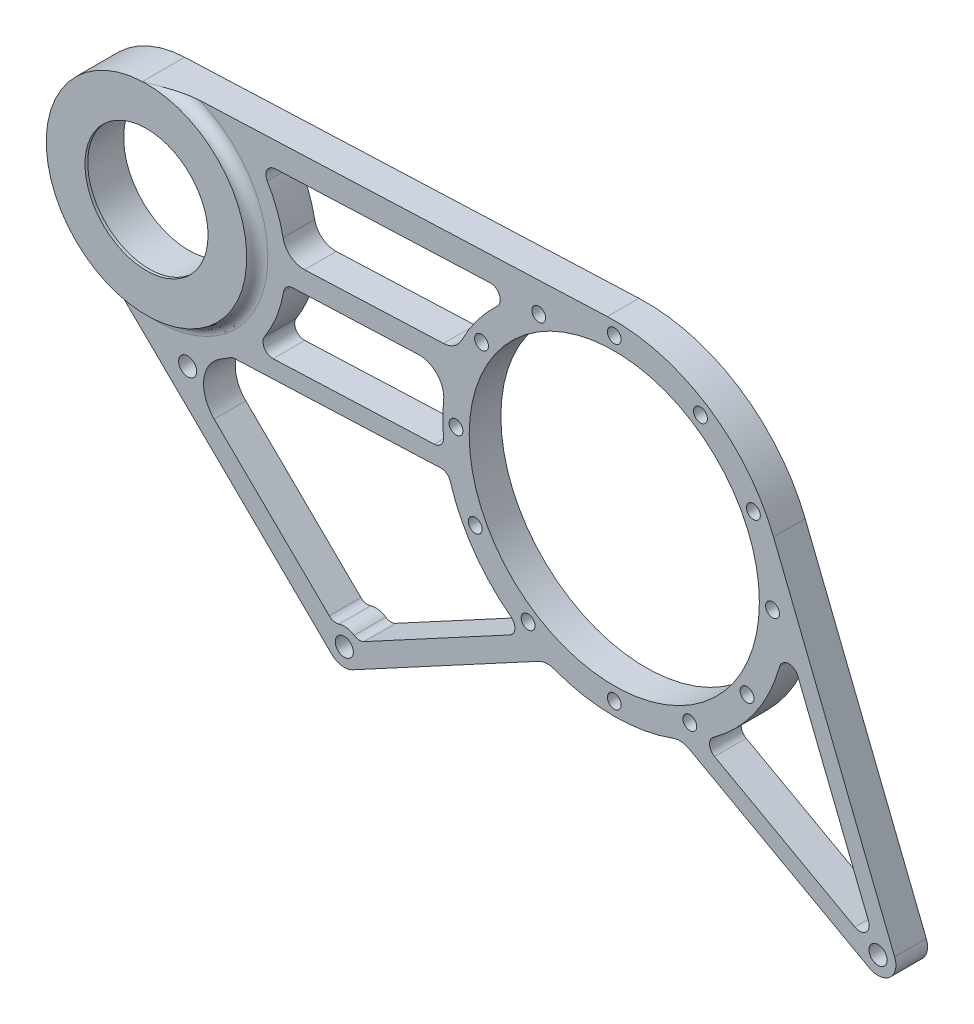
SolidWorks part; units mm, degrees
material "6061-T6 (SS)"
ref_plane "Front Plane" through (0, 0, 0) normal (0, 0, 1) x (1, 0, 0)
ref_plane "Top Plane" through (0, 0, 0) normal (0, 1, 0) x (1, 0, 0)
ref_plane "Right Plane" through (0, 0, 0) normal (1, 0, 0) x (0, 0, -1)
sketch "Sketch1" plane through (0, 0, 0) normal (0, 0, 1) x (1, 0, 0)
  line L0 (-114.3, 95.25) -> (-114.3, 107.95) construction
  line L1 (-280.8642, 163.1704) -> (-116.8043, 169.8118)
  line L2 (-304.7421, 101.1501) -> (-216.3071, 14.4521)
  line L3 (-13.0706, 21.4387) -> (-56.8054, 130.918)
  line L4 (-208.742, 13.3833) -> (-141.7118, 49.5504)
  line L5 (-22.1639, 13.4141) -> (-87.2342, 49.3665)
  circle A0 centre (-279.4, 127) radius 23.5
  circle A1 centre (-114.3, 95.25) radius 36 construction
  circle A2 centre (0, 0) radius 12.7 construction
  circle A3 centre (-228.6, 0) radius 12.7 construction
  circle A4 centre (-114.3, 107.95) radius 52.3875
  circle A5 centre (-19.05, 19.05) radius 3.2639
  circle A6 centre (-211.7995, 19.05) radius 3.2639
  circle A7 centre (-279.4, 127) radius 36.2
  arc A8 (-135.9521, 49.947) -> (-93.0137, 49.8118) centre (-114.3, 107.95) ccw
  arc A9 (-216.3071, 14.4521) -> (-208.742, 13.3833) centre (-211.7995, 19.05) ccw
  arc A10 (-22.1639, 13.4141) -> (-13.0706, 21.4387) centre (-19.05, 19.05) ccw
  arc A11 (-56.8054, 130.918) -> (-116.8043, 169.8118) centre (-114.3, 107.95) ccw
  arc A12 (-135.9521, 49.947) -> (-141.7118, 49.5504) centre (-138.3949, 43.4031) ccw
  arc A13 (-87.2342, 49.3665) -> (-93.0137, 49.8118) centre (-90.6122, 43.2526) ccw
  dimension "D5" = 72
  dimension "D6" = 47
  dimension "D7" = 25.4
  dimension "D8" = 25.4
  dimension "D11" = 104.775
  dimension "D14" = 6.5278
  dimension "D15" = 6.5278
  dimension "D16" = 25.4
  dimension "D17" = 12.7
  dimension "D18" = 123.825
  dimension "D19" = 3.175
  dimension "D20" = 6.985
  dimension "D21" = 6.985
  dimension "D1" = 114.3
  dimension "D2" = 95.25
  dimension "D3" = 279.4
  dimension "D4" = 127
  dimension "D9" = 228.6
  dimension "D10" = 12.7
  dimension "D12" = 19.05
  dimension "D13" = 19.05
extrude "Boss-Extrude1" add sketch "Sketch1" along normal blind 11.43 contours A13 L5 A10 L3 A11 L1 A7 L2 A9 L4 A12 A8 A6 A5 A4 | A7 A0 region at (-168.693, 91.0379, 0) region at (-255.035, 152.3713, 0)
sketch "Sketch2" plane through (0, 0, 11.43) normal (0, 0, 1) x (1, 0, 0)
  circle A0 centre (-279.4, 127) radius 36.2
  circle A1 centre (-279.4, 127) radius 23.5
extrude "Boss-Extrude2" add sketch "Sketch2" along normal blind 3.81
fillet "Fillet1" radius 3.81 1 edges at (-245.6173, 113.9936, 11.43)
sketch "Sketch3" plane through (0, 0, 11.43) normal (0, 0, 1) x (1, 0, 0)
  line L0 (-114.3, 107.95) -> (-114.3, 165.1) construction
  line L1 (-114.3, 107.95) -> (-57.15, 107.95) construction
  line L2 (-114.3, 107.95) -> (-83.1739, 155.88) construction
  line L3 (-114.3, 107.95) -> (-64.0756, 135.2196) construction
  circle A0 centre (-114.3, 107.95) radius 57.15 construction
  circle A11 centre (-114.3, 165.1) radius 2.5
  circle A12 centre (-57.15, 107.95) radius 2.5
  circle A13 centre (-114.3, 50.8) radius 2.5
  circle A14 centre (-171.45, 107.95) radius 2.5
  circle A15 centre (-83.1739, 155.88) radius 2.5
  circle A16 centre (-64.0756, 135.2196) radius 2.5
  circle A17 centre (-66.37, 76.8239) radius 2.5
  circle A18 centre (-87.0304, 57.7256) radius 2.5
  circle A19 centre (-145.4261, 60.02) radius 2.5
  circle A20 centre (-164.5244, 80.6804) radius 2.5
  circle A21 centre (-162.23, 139.0761) radius 2.5
  circle A22 centre (-141.5696, 158.1744) radius 2.5
  point P14 (-114.3, 107.95)
  point P25 (-114.3, 107.95)
  point P33 (-114.3, 107.95)
  dimension "D1" = 114.3
  dimension "D2" = 5
  dimension "D6" = 5
  dimension "D4" = 33
  dimension "D5" = 61.5
  dimension "D3" = 4
  dimension "D7" = 4
extrude "5mm Holes" cut sketch "Sketch3" against normal through all
sketch "Sketch4" plane through (0, 0, 15.24) normal (0, 0, 1) x (1, 0, 0)
  circle A0 centre (-279.4, 127) radius 22.225
  circle A1 centre (-279.4, 127) radius 23.5 construction
  circle A2 centre (-279.4, 127) radius 23.5
  dimension "D1" = 44.45
extrude "Boss-Extrude3" add sketch "Sketch4" against normal blind 1
sketch "Sketch5" plane through (0, 0, 11.43) normal (0, 0, 1) x (1, 0, 0)
  line L0 (-48.0193, 91.8071) -> (-22.5033, 27.9342)
  line L1 (-13.0706, 21.4387) -> (-56.8054, 130.918) construction
  line L2 (-78.1047, 51.5771) -> (-27.4356, 23.5816)
  line L3 (-22.1639, 13.4141) -> (-87.2342, 49.3665) construction
  line L4 (-236.7455, 156.0591) -> (-159.125, 159.2013)
  line L5 (-263.8382, 163.8596) -> (-116.8043, 169.8118) construction
  line L6 (-226.1253, 129.7972) -> (-175.9845, 131.827)
  line L7 (-230.4174, 121.9972) -> (-185.1154, 123.8311)
  line L8 (-258.7869, 66.7686) -> (-217.2302, 26.028)
  line L9 (-204.6483, 24.2506) -> (-152.0143, 52.6499)
  line L10 (-292.5742, 89.2212) -> (-216.3071, 14.4521) construction
  line L11 (-208.742, 13.3833) -> (-141.7118, 49.5504) construction
  line L12 (-237.4937, 96.2899) -> (-179.3047, 98.6455)
  line L13 (-251.3498, 89.3738) -> (-177.0086, 92.3833)
  arc A0 (-175.0426, 119.9291) -> (-175.9673, 102.4457) centre (-114.3, 107.95) ccw construction
  circle A1 centre (-211.7995, 19.05) radius 6.4389 construction
  circle A2 centre (-19.05, 19.05) radius 6.4389 construction
  arc A3 (-54.6287, 91.4427) -> (-78.4387, 57.481) centre (-114.3, 107.95) cw
  arc A4 (-48.0193, 91.8071) -> (-54.6287, 91.4427) centre (-51.2626, 90.5115) ccw
  arc A5 (-27.4356, 23.5816) -> (-22.5033, 27.9342) centre (-25.7466, 26.6385) ccw
  arc A6 (-78.1047, 51.5771) -> (-78.4387, 57.481) centre (-76.4157, 54.634) cw
  arc A7 (-233.9104, 135.9413) -> (-239.6024, 150.7781) centre (-279.4, 127) ccw construction
  arc A8 (-292.5742, 89.2212) -> (-263.8382, 163.8596) centre (-279.4, 127) ccw construction
  arc A9 (-213.7352, 25.191) -> (-208.2383, 24.4145) centre (-211.7995, 19.05) cw
  arc A10 (-156.5977, 153.1613) -> (-169.499, 135.9897) centre (-114.3, 107.95) ccw
  arc A11 (-175.9093, 114.0697) -> (-175.9673, 102.4457) centre (-114.3, 107.95) ccw
  arc A12 (-173.5263, 89.9112) -> (-151.5703, 58.5123) centre (-114.3, 107.95) ccw
  arc A13 (-239.6024, 150.7781) -> (-233.9104, 135.9413) centre (-279.4, 127) cw
  arc A14 (-233.7176, 119.1025) -> (-240.5609, 101.6865) centre (-279.4, 127) cw
  arc A15 (-240.5609, 101.6865) -> (-233.7176, 119.1025) centre (-279.4, 127) ccw construction
  arc A16 (-253.1835, 88.7646) -> (-256.2406, 86.8392) centre (-279.4, 127) cw
  arc A17 (-159.125, 159.2013) -> (-156.5977, 153.1613) centre (-158.9837, 155.7117) cw
  arc A20 (-236.7455, 156.0591) -> (-239.6024, 150.7781) centre (-236.6043, 152.5695) ccw
  arc A21 (-179.3047, 98.6455) -> (-175.9673, 102.4457) centre (-179.446, 102.1352) ccw
  arc A23 (-230.4174, 121.9972) -> (-233.7176, 119.1025) centre (-230.2762, 118.5075) ccw
  arc A24 (-237.4937, 96.2899) -> (-240.5609, 101.6865) centre (-237.6349, 99.7796) cw
  arc A25 (-217.2302, 26.028) -> (-213.7352, 25.191) centre (-214.7852, 28.522) ccw
  arc A26 (-204.6483, 24.2506) -> (-208.2383, 24.4145) centre (-206.3067, 27.3242) cw
  arc A27 (-152.0143, 52.6499) -> (-151.5703, 58.5123) centre (-153.6727, 55.7236) ccw
  arc A28 (-177.0086, 92.3833) -> (-173.5263, 89.9112) centre (-176.8673, 88.8936) cw
  arc A29 (-251.3498, 89.3738) -> (-253.1835, 88.7646) centre (-251.2085, 85.8842) ccw
  arc A31 (-173.5263, 89.9112) -> (-170.4887, 133.9499) centre (-114.3, 107.95) ccw construction
  arc A32 (-273.3418, 81.0375) -> (-253.1835, 88.7646) centre (-279.4, 127) ccw construction
  arc A33 (-258.7869, 66.7686) -> (-256.2406, 86.8392) centre (-249.8962, 75.8374) cw
  arc A34 (-169.499, 135.9897) -> (-175.9845, 131.827) centre (-176.2928, 139.4407) cw
  arc A35 (-233.9104, 135.9413) -> (-226.1253, 129.7972) centre (-226.4335, 137.411) ccw
  arc A36 (-185.1154, 123.8311) -> (-175.9093, 114.0697) centre (-184.7558, 114.9484) cw
  point P17 (-52.5701, 103.1988)
  point P23 (-83.2204, 54.4036)
  point P51 (-148.3837, 159.6362)
  point P54 (-171.3442, 132.0148)
  point P60 (-243.0732, 155.8029)
  point P63 (-175.5324, 98.7982)
  point P66 (-174.02, 124.2803)
  point P75 (-215.4925, 24.3245)
  point P78 (-206.7898, 23.0951)
  point P81 (-146.981, 55.3657)
  point P84 (-174.2524, 92.4948)
  point P90 (-273.3418, 81.0375)
  dimension "D1" = 123.825
  dimension "D2" = 12.8778
  dimension "D5" = 3.4925
  dimension "D6" = 6.35
  dimension "D14" = 3.4925
  dimension "D15" = 12.7
  dimension "D16" = 7.62
  dimension "D17" = 7.62
  dimension "D18" = 8.89
  dimension "D3" = 6.35
  dimension "D4" = 6.35
  dimension "D7" = 8.89
  dimension "D8" = 7.62
  dimension "D9" = 7.62
  dimension "D10" = 7.62
  dimension "D11" = 6.35
  dimension "D12" = 25.4
  dimension "D13" = 26.67
extrude "Cut-Extrude2" cut sketch "Sketch5" against normal through all both and the other way through all
ref_axis "Axis2" through (-279.4, 127, 14.24) along (0, 0, -1)
ref_axis "Axis1" through (-114.3, 107.95, 11.43) along (0, 0, -1)
ref_plane "Plane1" through (-114.3, 0, 0) normal (1, 0, 0) x (0, 0, -1)
ref_plane "Plane2" through (-279.4, 0, 0) normal (1, 0, 0) x (0, 0, -1)
ref_plane "Plane3" through (0, 0, 5.715) normal (0, 0, -1) x (-1, 0, 0)
ref_plane "Plane4" through (0, 0, 7.12) normal (0, 0, -1) x (-1, 0, 0)
split line "Split Line1" [suppressed]
split line "Split Line2" [suppressed]
sketch "Sketch6" [suppressed] plane through (0, 0, 5.715) normal (0, 0, -1) x (-1, 0, 0)
  circle A1 centre (114.3, 107.95) radius 52.3875 construction
sketch "Sketch7" plane through (0, 0, 7.12) normal (0, 0, -1) x (-1, 0, 0)
  circle A0 centre (279.4, 127) radius 23.5
sketch "Sketch8" plane through (0, 0, 11.43) normal (0, 0, 1) x (1, 0, 0)
  circle A0 centre (-268.3542, 78.4783) radius 3.2639
extrude "Cut-Extrude3" cut sketch "Sketch8" against normal through all both and the other way through all
ref_point "Puck Center" [suppressed]
ref_point "Bearing Center"
sketch "Sketch9" [suppressed] plane through (0, 0, 0) normal (0, 0, 1) x (1, 0, 0)
  line L0 (-210.8988, 25.4256) -> (-210.8988, 91.0113) construction
  line L1 (-177.0086, 92.3833) -> (-251.3498, 89.3738) construction
  line L2 (-236.1159, 143.6054) -> (-163.7987, 145.1392) construction
  circle A0 centre (-114.3, 107.95) radius 31.75 construction
  arc A1 (-208.2383, 24.4145) -> (-213.7352, 25.191) centre (-211.7995, 19.05) ccw construction
  circle A2 centre (-210.8988, 77.2346) radius 5.08
  circle A3 centre (-210.8988, 45.0623) radius 5.08
  circle A4 centre (-146.05, 107.95) radius 5.08
  circle A5 centre (-114.3, 139.7) radius 5.08
  circle A6 centre (-82.55, 107.95) radius 5.08
  circle A7 centre (-114.3, 76.2) radius 5.08
  arc A8 (-233.9104, 135.9413) -> (-239.6024, 150.7781) centre (-279.4, 127) ccw construction
  arc A9 (-156.5977, 153.1613) -> (-169.499, 135.9897) centre (-114.3, 107.95) ccw construction
  circle A10 centre (-199.9573, 144.3723) radius 5.08
  point P0 (-48.5383, 56.2255)
  point P8 (-146.05, 107.95)
  point P30 (-114.3, 107.95)
  dimension "D1" = 63.5
  dimension "D2" = 10.16
  dimension "D3" = 10.16
  dimension "D4" = 10.16
  dimension "D6" = 10.16
  dimension "D5" = 4
sketch "Sketch10" [suppressed] plane through (0, 0, 0) normal (0, 0, -1) x (-1, 0, 0)
  line L0 (202.0088, 77.2346) -> (202.0088, 45.0623)
  line L1 (219.7888, 77.2346) -> (219.7888, 45.0623)
  circle A0 centre (114.3, 107.95) radius 38.1
  circle A1 centre (199.9573, 144.3723) radius 8.89
  circle A2 centre (199.9573, 144.3723) radius 5.08
  circle A3 centre (199.9573, 144.3723) radius 5.08 construction
  circle A4 centre (146.05, 107.95) radius 5.08
  circle A5 centre (146.05, 107.95) radius 5.08 construction
  circle A6 centre (210.8988, 45.0623) radius 5.08
  circle A7 centre (210.8988, 45.0623) radius 5.08 construction
  circle A8 centre (210.8988, 77.2346) radius 5.08
  circle A9 centre (210.8988, 77.2346) radius 5.08 construction
  circle A10 centre (114.3, 76.2) radius 5.08
  circle A11 centre (114.3, 76.2) radius 5.08 construction
  circle A12 centre (82.55, 107.95) radius 5.08
  circle A13 centre (82.55, 107.95) radius 5.08 construction
  circle A14 centre (114.3, 139.7) radius 5.08
  circle A15 centre (114.3, 139.7) radius 5.08 construction
  arc A16 (219.7888, 77.2346) -> (202.0088, 77.2346) centre (210.8988, 77.2346) ccw
  arc A17 (202.0088, 45.0623) -> (219.7888, 45.0623) centre (210.8988, 45.0623) ccw
  circle A18 centre (210.8988, 45.0623) radius 8.89 construction
  circle A19 centre (210.8988, 77.2346) radius 8.89 construction
  dimension "D1" = 76.2
  dimension "D9" = 3.81
  dimension "D2" = 0
  dimension "D3" = 0
  dimension "D4" = 0
  dimension "D5" = 0
  dimension "D6" = 0
  dimension "D7" = 0
  dimension "D8" = 0
  dimension "D10" = 3.81
